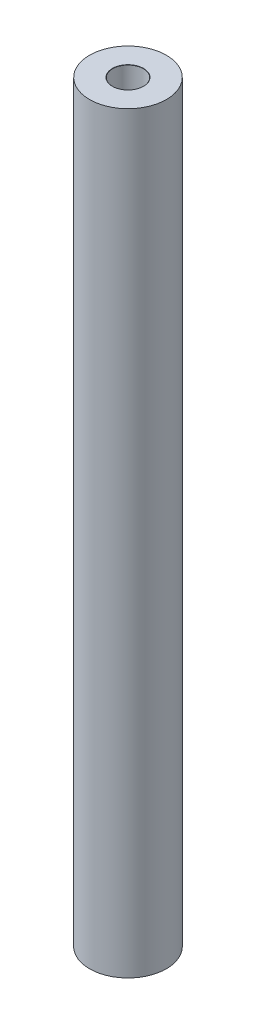
SolidWorks part; units mm, degrees
material "6061-T4 (SS)"
ref_plane "Front Plane" through (0, 0, 0) normal (0, 0, 1) x (1, 0, 0)
ref_plane "Top Plane" through (0, 0, 0) normal (0, 1, 0) x (1, 0, 0)
ref_plane "Right Plane" through (0, 0, 0) normal (1, 0, 0) x (0, 0, -1)
sketch "Sketch1" plane through (0, 0, 0) normal (0, 1, 0) x (1, 0, 0)
  circle A0 centre (0, 0) radius 5
  dimension "D1" = 10
extrude "Boss-Extrude1" add sketch "Sketch1" along normal blind 98
hole_wizard "Ø4.0mm Dowel Hole1" positions "3DSketch1" profile "Sketch4" hole size "Ø4.0" standard "ANSI Metric"
sketch3d "3DSketch1"
  line L0 (0, 98, 0) -> (0, 0, 0) construction
  point P0 (0, 98, 0)
  point P5 (0, 0, 0)
sketch "Sketch4" plane through (0, 98, 0) normal (1, 0, 0) x (0, 0, 1)
  line L0 (0, 0) -> (0, 14.2017)
  line L1 (0, 14.2017) -> (2, 13)
  line L2 (2, 13) -> (2, 0.025)
  line L3 (2, 0.025) -> (2.025, 0)
  line L5 (2.025, 0) -> (0, 0)
  line L6 (-2, 0.025) -> (-2.025, 0) construction
  line L10 (0, 14.2017) -> (-2, 13) construction
  line L11 (0, -6.35) -> (0, 107.95) construction
  dimension "Hole Dia." = 4
  dimension "Hole Depth" = 13
  dimension "Near C'Sink Dia." = 4.05
  dimension "Near C'Sink Angle" = 90
  dimension "Drill Angle" = 118
cosmetic thread "Cosmetic Thread1" parameters "D1"=10, "D2"=5
ref_plane "Plane3" through (0, 49, 0) normal (0, 1, 0) x (1, 0, 0)
mirror "Mirror1" about plane through (0, 49, 0) normal (0, 1, 0) of "Ø4.0mm Dowel Hole1"
cosmetic thread "Cosmetic Thread2" parameters "D1"=10, "D2"=5
equation "\"D1@Boss-Extrude1\"=98"
